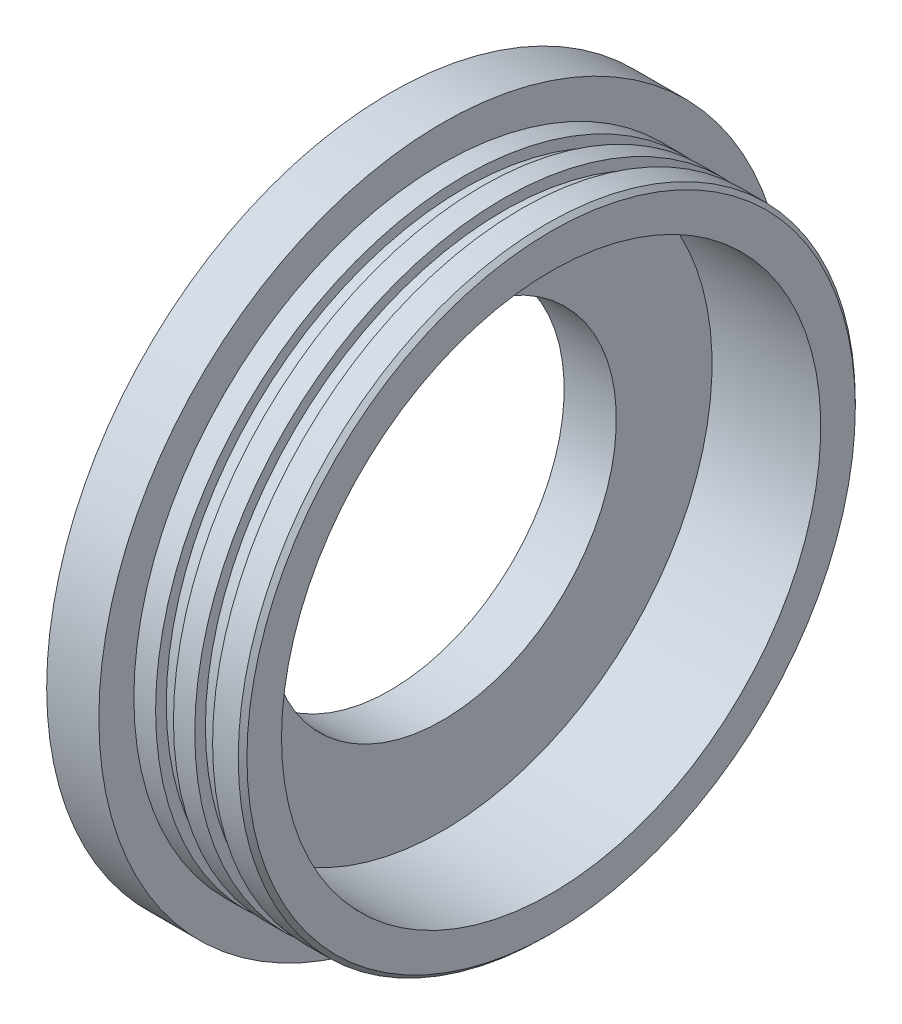
SolidWorks part; units mm, degrees
material "6061-T6 (SS)"
ref_plane "正面" through (0, 0, 0) normal (0, 0, 1) x (1, 0, 0)
ref_plane "平面" through (0, 0, 0) normal (0, 1, 0) x (1, 0, 0)
ref_plane "右側面" through (0, 0, 0) normal (1, 0, 0) x (0, 0, -1)
sketch "ｽｹｯﾁ1" plane through (0, 0, 0) normal (0, 0, 1) x (1, 0, 0)
  line L0 (0, 0) -> (35, 0) construction
  line L1 (-12, 40) -> (-12, 79)
  line L2 (-12, 79) -> (0, 79)
  line L3 (0, 79) -> (0, 70.95)
  line L4 (0, 70.95) -> (25, 70.95)
  line L5 (25, 70.95) -> (25, 62)
  line L6 (25, 62) -> (0, 62)
  line L7 (0, 62) -> (0, 40)
  line L8 (0, 40) -> (-12, 40)
  dimension "D1" = 12
  dimension "D2" = 25
  dimension "D3" = 79
  dimension "D4" = 70.95
  dimension "D5" = 62
  dimension "D6" = 40
revolve "外形旋削" add sketch "ｽｹｯﾁ1" angle 360 about L0
chamfer "はめ込み先端 面取り" distance 1 angle 45 1 edges at (25, 0, 70.95)
sketch "ｽｹｯﾁ2" plane through (0, 0, 0) normal (0, 0, 1) x (1, 0, 0)
  line L0 (0, 0) -> (35, 0) construction
  line L1 (5, 68.5) -> (9.1, 68.5)
  line L2 (9.1, 68.5) -> (9.1, 70.95)
  line L3 (9.1, 70.95) -> (5, 70.95)
  line L4 (5, 70.95) -> (5, 68.5)
  dimension "D4" = 70.95
  dimension "D1" = 9.1
  dimension "D2" = 5
  dimension "D3" = 68.5
revolve "Oリング溝入れ G-135" cut sketch "ｽｹｯﾁ2" angle 360 about L0
ref_axis "中心軸" through (-14.35, 0, 0) along (1, 0, 0)
pattern_linear "Oリング溝 2 本目" count 2 spacing 9 along (1, 0, 0) of "Oリング溝入れ G-135"
sketch "ｽｹｯﾁ3" plane through (0, 0, 0) normal (0, 0, 1) x (1, 0, 0)
  line L0 (0, 0) -> (35, 0) construction
  line L1 (-12, 42.5) -> (-9.6, 42.5)
  line L2 (-9.6, 42.5) -> (-9.6, 46.6)
  line L3 (-9.6, 46.6) -> (-12, 46.6)
  line L4 (-12, 46.6) -> (-12, 42.5)
  dimension "D1" = 9.6
  dimension "D2" = 12
  dimension "D3" = 42.5
  dimension "D4" = 46.6
revolve "窓 Oリング溝入れ G-85" cut sketch "ｽｹｯﾁ3" angle 360 about L0
hole_wizard "M4 めねじ" positions "ｽｹｯﾁ5" profile "ｽｹｯﾁ4" tap size "M4" standard "JIS"
sketch "ｽｹｯﾁ5" plane through (-12, 0, 0) normal (-1, 0, 0) x (0, 0, 1)
  point P0 (0, 54.25)
  dimension "D1" = 54.25
sketch "ｽｹｯﾁ4" plane through (-12, 54.25, 0) normal (0, 1, 0) x (0, 0, 1)
  line L0 (0, 0) -> (0, 10.9914)
  line L1 (0, 10.9914) -> (1.65, 10)
  line L2 (1.65, 10) -> (1.65, 0)
  line L5 (1.65, 0) -> (0, 0)
  line L10 (0, 10.9914) -> (-1.65, 10) construction
  line L11 (0, -6.35) -> (0, 107.95) construction
  dimension "ねじ下穴ﾄﾞﾘﾙ直径" = 3.3
  dimension "ねじ下穴ﾄﾞﾘﾙの深さ" = 10
  dimension "ﾄﾞﾘﾙ角度" = 118
cosmetic thread "穴のねじ山1" parameters "D1"=8, "D2"=4
pattern_circular "M4 めねじ 等配" count 6 over 360 about axis through (-14.35, 0, 0) along (1, 0, 0) of "M4 めねじ"
equation "\"CAP_PLATE_T\" = 12"
equation "\"D1@ｽｹｯﾁ1\" = \"CAP_PLATE_T\""
equation "\"SPIGOT_LEN\" = 25"
equation "\"D2@ｽｹｯﾁ1\" = \"SPIGOT_LEN\""
equation "\"FLANGE_OD\" = 158"
equation "\"D3@ｽｹｯﾁ1\" = \"FLANGE_OD\" / 2"
equation "\"SPIGOT_OD\" = 141.9"
equation "\"D4@ｽｹｯﾁ1\" = \"SPIGOT_OD\" / 2"
equation "\"SPIGOT_ID\" = 124"
equation "\"D5@ｽｹｯﾁ1\" = \"SPIGOT_ID\" / 2"
equation "\"WINDOW_APERTURE\" = 80"
equation "\"D6@ｽｹｯﾁ1\" = \"WINDOW_APERTURE\" / 2"
equation "\"SPIGOT_C\" = 1"
equation "\"D1@はめ込み先端 面取り\" = \"SPIGOT_C\""
equation "\"GROOVE_POS\" = 5"
equation "\"GROOVE_W\" = 4.1"
equation "\"D1@ｽｹｯﾁ2\" = \"GROOVE_POS\" + \"GROOVE_W\""
equation "\"D2@ｽｹｯﾁ2\" = \"GROOVE_POS\""
equation "\"GROOVE_D\" = 137"
equation "\"D3@ｽｹｯﾁ2\" = \"GROOVE_D\" / 2"
equation "\"D4@ｽｹｯﾁ2\" = \"SPIGOT_OD\" / 2"
equation "\"GROOVE_PITCH\" = 9"
equation "\"D3@Oリング溝 2 本目\" = \"GROOVE_PITCH\""
equation "\"FACE_GROOVE_H\" = 2.4"
equation "\"D1@ｽｹｯﾁ3\" = abs( -\"CAP_PLATE_T\" + \"FACE_GROOVE_H\" )"
equation "\"D2@ｽｹｯﾁ3\" = \"CAP_PLATE_T\""
equation "\"FACE_GROOVE_ID\" = 85"
equation "\"D3@ｽｹｯﾁ3\" = \"FACE_GROOVE_ID\" / 2"
equation "\"FACE_GROOVE_W\" = 4.1"
equation "\"D4@ｽｹｯﾁ3\" = \"FACE_GROOVE_ID\" / 2 + \"FACE_GROOVE_W\""
equation "\"RING_PCD\" = 108.5"
equation "\"D1@ｽｹｯﾁ5\" = \"RING_PCD\" / 2"
